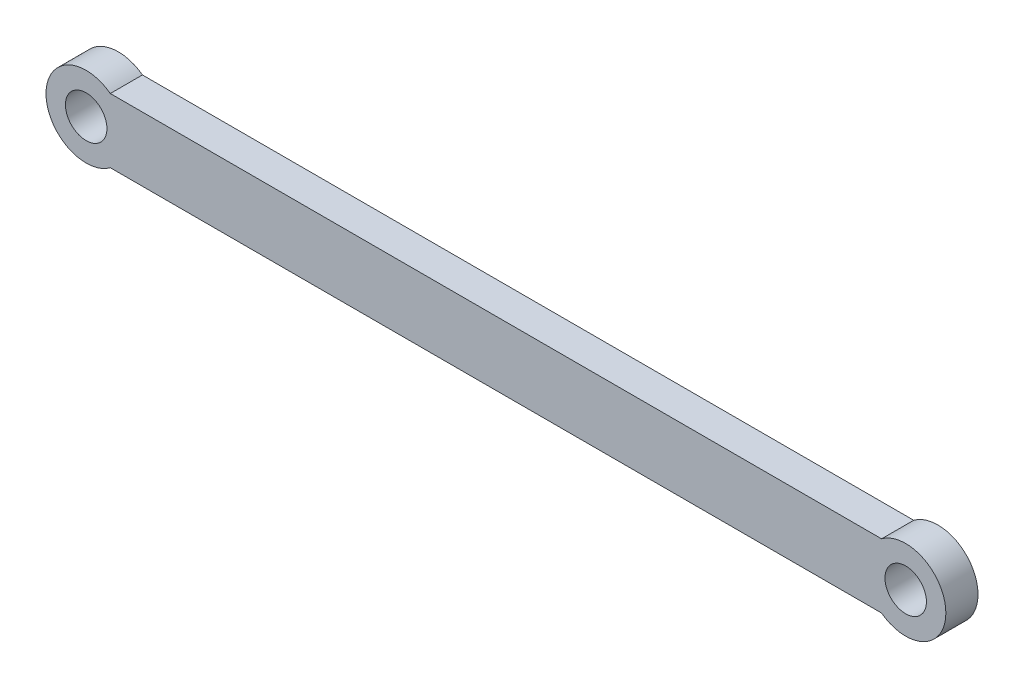
SolidWorks part; units mm, degrees
ref_plane "Front Plane" through (0, 0, 0) normal (0, 0, 1) x (1, 0, 0)
ref_plane "Top Plane" through (0, 0, 0) normal (0, 1, 0) x (1, 0, 0)
ref_plane "Right Plane" through (0, 0, 0) normal (1, 0, 0) x (0, 0, -1)
sketch "Sketch1" plane through (0, 0, 0) normal (0, 0, 1) x (1, 0, 0)
  line L1 (4.7625, 0) -> (157.1625, 0)
  line L3 (4.7625, 12.7) -> (157.1625, 12.7)
  arc A0 (4.7625, 12.7) -> (4.7625, 0) centre (0, 6.35) ccw
  arc A1 (157.1625, 0) -> (157.1625, 12.7) centre (161.925, 6.35) ccw
  dimension "D3" = 15.875
  dimension "D4" = 15.875
extrude "Boss-Extrude1" add sketch "Sketch1" along normal blind 6.35
sketch "Sketch2" plane through (0, 0, 0) normal (0, 0, -1) x (-1, 0, 0)
  circle A0 centre (-161.925, 6.35) radius 4.0958
  arc A1 (-157.1625, 12.7) -> (-157.1625, 0) centre (-161.925, 6.35) ccw construction
  circle A2 centre (0, 6.35) radius 4.0957
  arc A3 (-4.7625, 0) -> (-4.7625, 12.7) centre (0, 6.35) ccw construction
  dimension "D1" = 8.1915
  dimension "D2" = 8.1915
extrude "Cut-Extrude1" cut sketch "Sketch2" against normal up to surface (6.35 mm away) up to face at (80.9625, 6.35, 6.35)
